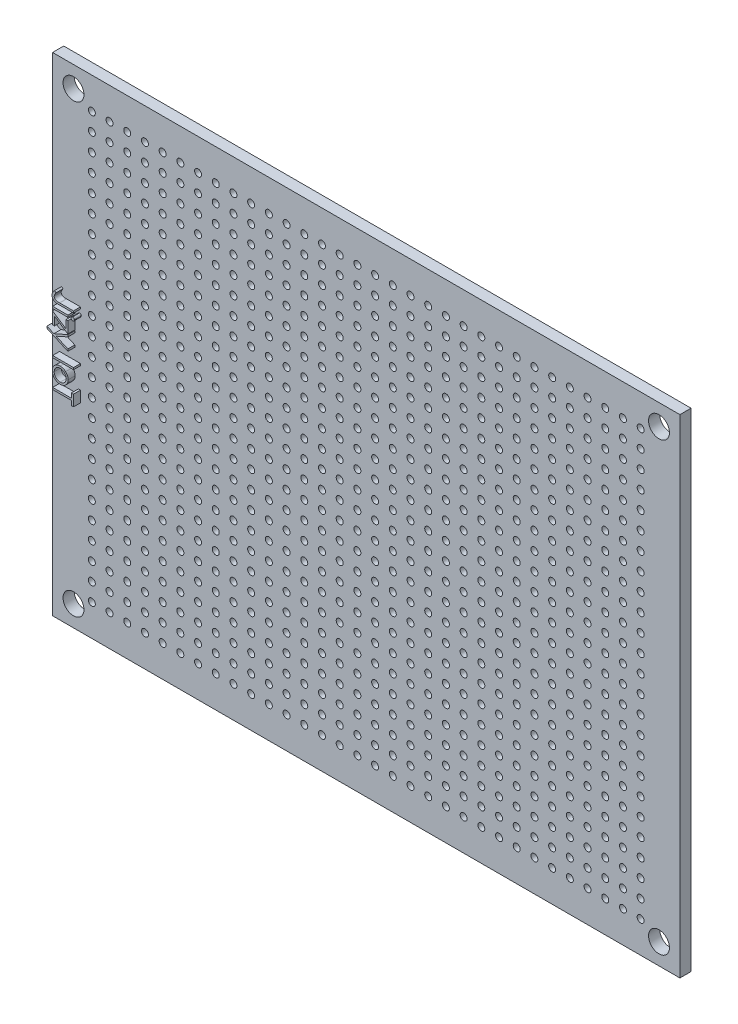
SolidWorks part; units mm, degrees
ref_plane "Front Plane" through (0, 0, 0) normal (0, 0, 1) x (1, 0, 0)
ref_plane "Top Plane" through (0, 0, 0) normal (0, 1, 0) x (1, 0, 0)
ref_plane "Right Plane" through (0, 0, 0) normal (1, 0, 0) x (0, 0, -1)
sketch "Sketch1" plane through (0, 0, 0) normal (0, 0, 1) x (1, 0, 0)
  line L0 (42, 32) -> (-42, 32) construction
  line L1 (45, -35) -> (-45, -35)
  line L2 (45, -35) -> (45, 35)
  line L3 (45, 35) -> (-45, 35)
  line L4 (-45, -35) -> (-45, 35)
  line L5 (45, -35) -> (-45, 35) construction
  line L6 (45, 35) -> (-45, -35) construction
  line L7 (-42, -32) -> (-42, 32) construction
  line L8 (42, -32) -> (-42, -32) construction
  line L9 (42, -32) -> (42, 32) construction
  line L10 (-60.0579, 0) -> (53.9786, 0) construction
  circle A0 centre (-42, 32) radius 1.5
  circle A1 centre (42, 32) radius 1.5
  circle A2 centre (42, -32) radius 1.5
  circle A3 centre (-42, -32) radius 1.5
  circle A4 centre (-39.37, 30.48) radius 0.5
  circle A5 centre (-36.83, 30.48) radius 0.5
  circle A6 centre (-34.29, 30.48) radius 0.5
  circle A7 centre (-31.75, 30.48) radius 0.5
  circle A8 centre (-29.21, 30.48) radius 0.5
  circle A9 centre (-26.67, 30.48) radius 0.5
  circle A10 centre (-24.13, 30.48) radius 0.5
  circle A11 centre (-21.59, 30.48) radius 0.5
  circle A12 centre (-19.05, 30.48) radius 0.5
  circle A13 centre (-16.51, 30.48) radius 0.5
  circle A14 centre (-13.97, 30.48) radius 0.5
  circle A15 centre (-11.43, 30.48) radius 0.5
  circle A16 centre (-8.89, 30.48) radius 0.5
  circle A17 centre (-6.35, 30.48) radius 0.5
  circle A18 centre (-3.81, 30.48) radius 0.5
  circle A19 centre (-1.27, 30.48) radius 0.5
  circle A20 centre (1.27, 30.48) radius 0.5
  circle A21 centre (3.81, 30.48) radius 0.5
  circle A22 centre (6.35, 30.48) radius 0.5
  circle A23 centre (8.89, 30.48) radius 0.5
  circle A24 centre (11.43, 30.48) radius 0.5
  circle A25 centre (13.97, 30.48) radius 0.5
  circle A26 centre (16.51, 30.48) radius 0.5
  circle A27 centre (19.05, 30.48) radius 0.5
  circle A28 centre (21.59, 30.48) radius 0.5
  circle A29 centre (24.13, 30.48) radius 0.5
  circle A30 centre (26.67, 30.48) radius 0.5
  circle A31 centre (29.21, 30.48) radius 0.5
  circle A32 centre (31.75, 30.48) radius 0.5
  circle A33 centre (34.29, 30.48) radius 0.5
  circle A34 centre (36.83, 30.48) radius 0.5
  circle A35 centre (39.37, 30.48) radius 0.5
  circle A36 centre (-36.83, 27.94) radius 0.5
  circle A37 centre (-34.29, 27.94) radius 0.5
  circle A38 centre (-31.75, 27.94) radius 0.5
  circle A39 centre (-29.21, 27.94) radius 0.5
  circle A40 centre (-26.67, 27.94) radius 0.5
  circle A41 centre (-24.13, 27.94) radius 0.5
  circle A42 centre (-21.59, 27.94) radius 0.5
  circle A43 centre (-19.05, 27.94) radius 0.5
  circle A44 centre (-16.51, 27.94) radius 0.5
  circle A45 centre (-13.97, 27.94) radius 0.5
  circle A46 centre (-11.43, 27.94) radius 0.5
  circle A47 centre (-8.89, 27.94) radius 0.5
  circle A48 centre (-6.35, 27.94) radius 0.5
  circle A49 centre (-3.81, 27.94) radius 0.5
  circle A50 centre (-1.27, 27.94) radius 0.5
  circle A51 centre (1.27, 27.94) radius 0.5
  circle A52 centre (3.81, 27.94) radius 0.5
  circle A53 centre (6.35, 27.94) radius 0.5
  circle A54 centre (8.89, 27.94) radius 0.5
  circle A55 centre (11.43, 27.94) radius 0.5
  circle A56 centre (13.97, 27.94) radius 0.5
  circle A57 centre (16.51, 27.94) radius 0.5
  circle A58 centre (19.05, 27.94) radius 0.5
  circle A59 centre (21.59, 27.94) radius 0.5
  circle A60 centre (24.13, 27.94) radius 0.5
  circle A61 centre (26.67, 27.94) radius 0.5
  circle A62 centre (29.21, 27.94) radius 0.5
  circle A63 centre (31.75, 27.94) radius 0.5
  circle A64 centre (34.29, 27.94) radius 0.5
  circle A65 centre (36.83, 27.94) radius 0.5
  circle A66 centre (39.37, 27.94) radius 0.5
  circle A67 centre (-36.83, 25.4) radius 0.5
  circle A68 centre (-34.29, 25.4) radius 0.5
  circle A69 centre (-31.75, 25.4) radius 0.5
  circle A70 centre (-29.21, 25.4) radius 0.5
  circle A71 centre (-26.67, 25.4) radius 0.5
  circle A72 centre (-24.13, 25.4) radius 0.5
  circle A73 centre (-21.59, 25.4) radius 0.5
  circle A74 centre (-19.05, 25.4) radius 0.5
  circle A75 centre (-16.51, 25.4) radius 0.5
  circle A76 centre (-13.97, 25.4) radius 0.5
  circle A77 centre (-11.43, 25.4) radius 0.5
  circle A78 centre (-8.89, 25.4) radius 0.5
  circle A79 centre (-6.35, 25.4) radius 0.5
  circle A80 centre (-3.81, 25.4) radius 0.5
  circle A81 centre (-1.27, 25.4) radius 0.5
  circle A82 centre (1.27, 25.4) radius 0.5
  circle A83 centre (3.81, 25.4) radius 0.5
  circle A84 centre (6.35, 25.4) radius 0.5
  circle A85 centre (8.89, 25.4) radius 0.5
  circle A86 centre (11.43, 25.4) radius 0.5
  circle A87 centre (13.97, 25.4) radius 0.5
  circle A88 centre (16.51, 25.4) radius 0.5
  circle A89 centre (19.05, 25.4) radius 0.5
  circle A90 centre (21.59, 25.4) radius 0.5
  circle A91 centre (24.13, 25.4) radius 0.5
  circle A92 centre (26.67, 25.4) radius 0.5
  circle A93 centre (29.21, 25.4) radius 0.5
  circle A94 centre (31.75, 25.4) radius 0.5
  circle A95 centre (34.29, 25.4) radius 0.5
  circle A96 centre (36.83, 25.4) radius 0.5
  circle A97 centre (39.37, 25.4) radius 0.5
  circle A98 centre (-36.83, 22.86) radius 0.5
  circle A99 centre (-34.29, 22.86) radius 0.5
  circle A100 centre (-31.75, 22.86) radius 0.5
  circle A101 centre (-29.21, 22.86) radius 0.5
  circle A102 centre (-26.67, 22.86) radius 0.5
  circle A103 centre (-24.13, 22.86) radius 0.5
  circle A104 centre (-21.59, 22.86) radius 0.5
  circle A105 centre (-19.05, 22.86) radius 0.5
  circle A106 centre (-16.51, 22.86) radius 0.5
  circle A107 centre (-13.97, 22.86) radius 0.5
  circle A108 centre (-11.43, 22.86) radius 0.5
  circle A109 centre (-8.89, 22.86) radius 0.5
  circle A110 centre (-6.35, 22.86) radius 0.5
  circle A111 centre (-3.81, 22.86) radius 0.5
  circle A112 centre (-1.27, 22.86) radius 0.5
  circle A113 centre (1.27, 22.86) radius 0.5
  circle A114 centre (3.81, 22.86) radius 0.5
  circle A115 centre (6.35, 22.86) radius 0.5
  circle A116 centre (8.89, 22.86) radius 0.5
  circle A117 centre (11.43, 22.86) radius 0.5
  circle A118 centre (13.97, 22.86) radius 0.5
  circle A119 centre (16.51, 22.86) radius 0.5
  circle A120 centre (19.05, 22.86) radius 0.5
  circle A121 centre (21.59, 22.86) radius 0.5
  circle A122 centre (24.13, 22.86) radius 0.5
  circle A123 centre (26.67, 22.86) radius 0.5
  circle A124 centre (29.21, 22.86) radius 0.5
  circle A125 centre (31.75, 22.86) radius 0.5
  circle A126 centre (34.29, 22.86) radius 0.5
  circle A127 centre (36.83, 22.86) radius 0.5
  circle A128 centre (39.37, 22.86) radius 0.5
  circle A129 centre (-36.83, 20.32) radius 0.5
  circle A130 centre (-34.29, 20.32) radius 0.5
  circle A131 centre (-31.75, 20.32) radius 0.5
  circle A132 centre (-29.21, 20.32) radius 0.5
  circle A133 centre (-26.67, 20.32) radius 0.5
  circle A134 centre (-24.13, 20.32) radius 0.5
  circle A135 centre (-21.59, 20.32) radius 0.5
  circle A136 centre (-19.05, 20.32) radius 0.5
  circle A137 centre (-16.51, 20.32) radius 0.5
  circle A138 centre (-13.97, 20.32) radius 0.5
  circle A139 centre (-11.43, 20.32) radius 0.5
  circle A140 centre (-8.89, 20.32) radius 0.5
  circle A141 centre (-6.35, 20.32) radius 0.5
  circle A142 centre (-3.81, 20.32) radius 0.5
  circle A143 centre (-1.27, 20.32) radius 0.5
  circle A144 centre (1.27, 20.32) radius 0.5
  circle A145 centre (3.81, 20.32) radius 0.5
  circle A146 centre (6.35, 20.32) radius 0.5
  circle A147 centre (8.89, 20.32) radius 0.5
  circle A148 centre (11.43, 20.32) radius 0.5
  circle A149 centre (13.97, 20.32) radius 0.5
  circle A150 centre (16.51, 20.32) radius 0.5
  circle A151 centre (19.05, 20.32) radius 0.5
  circle A152 centre (21.59, 20.32) radius 0.5
  circle A153 centre (24.13, 20.32) radius 0.5
  circle A154 centre (26.67, 20.32) radius 0.5
  circle A155 centre (29.21, 20.32) radius 0.5
  circle A156 centre (31.75, 20.32) radius 0.5
  circle A157 centre (34.29, 20.32) radius 0.5
  circle A158 centre (36.83, 20.32) radius 0.5
  circle A159 centre (39.37, 20.32) radius 0.5
  circle A160 centre (-36.83, 17.78) radius 0.5
  circle A161 centre (-34.29, 17.78) radius 0.5
  circle A162 centre (-31.75, 17.78) radius 0.5
  circle A163 centre (-29.21, 17.78) radius 0.5
  circle A164 centre (-26.67, 17.78) radius 0.5
  circle A165 centre (-24.13, 17.78) radius 0.5
  circle A166 centre (-21.59, 17.78) radius 0.5
  circle A167 centre (-19.05, 17.78) radius 0.5
  circle A168 centre (-16.51, 17.78) radius 0.5
  circle A169 centre (-13.97, 17.78) radius 0.5
  circle A170 centre (-11.43, 17.78) radius 0.5
  circle A171 centre (-8.89, 17.78) radius 0.5
  circle A172 centre (-6.35, 17.78) radius 0.5
  circle A173 centre (-3.81, 17.78) radius 0.5
  circle A174 centre (-1.27, 17.78) radius 0.5
  circle A175 centre (1.27, 17.78) radius 0.5
  circle A176 centre (3.81, 17.78) radius 0.5
  circle A177 centre (6.35, 17.78) radius 0.5
  circle A178 centre (8.89, 17.78) radius 0.5
  circle A179 centre (11.43, 17.78) radius 0.5
  circle A180 centre (13.97, 17.78) radius 0.5
  circle A181 centre (16.51, 17.78) radius 0.5
  circle A182 centre (19.05, 17.78) radius 0.5
  circle A183 centre (21.59, 17.78) radius 0.5
  circle A184 centre (24.13, 17.78) radius 0.5
  circle A185 centre (26.67, 17.78) radius 0.5
  circle A186 centre (29.21, 17.78) radius 0.5
  circle A187 centre (31.75, 17.78) radius 0.5
  circle A188 centre (34.29, 17.78) radius 0.5
  circle A189 centre (36.83, 17.78) radius 0.5
  circle A190 centre (39.37, 17.78) radius 0.5
  circle A191 centre (-36.83, 15.24) radius 0.5
  circle A192 centre (-34.29, 15.24) radius 0.5
  circle A193 centre (-31.75, 15.24) radius 0.5
  circle A194 centre (-29.21, 15.24) radius 0.5
  circle A195 centre (-26.67, 15.24) radius 0.5
  circle A196 centre (-24.13, 15.24) radius 0.5
  circle A197 centre (-21.59, 15.24) radius 0.5
  circle A198 centre (-19.05, 15.24) radius 0.5
  circle A199 centre (-16.51, 15.24) radius 0.5
  circle A200 centre (-13.97, 15.24) radius 0.5
  circle A201 centre (-11.43, 15.24) radius 0.5
  circle A202 centre (-8.89, 15.24) radius 0.5
  circle A203 centre (-6.35, 15.24) radius 0.5
  circle A204 centre (-3.81, 15.24) radius 0.5
  circle A205 centre (-1.27, 15.24) radius 0.5
  circle A206 centre (1.27, 15.24) radius 0.5
  circle A207 centre (3.81, 15.24) radius 0.5
  circle A208 centre (6.35, 15.24) radius 0.5
  circle A209 centre (8.89, 15.24) radius 0.5
  circle A210 centre (11.43, 15.24) radius 0.5
  circle A211 centre (13.97, 15.24) radius 0.5
  circle A212 centre (16.51, 15.24) radius 0.5
  circle A213 centre (19.05, 15.24) radius 0.5
  circle A214 centre (21.59, 15.24) radius 0.5
  circle A215 centre (24.13, 15.24) radius 0.5
  circle A216 centre (26.67, 15.24) radius 0.5
  circle A217 centre (29.21, 15.24) radius 0.5
  circle A218 centre (31.75, 15.24) radius 0.5
  circle A219 centre (34.29, 15.24) radius 0.5
  circle A220 centre (36.83, 15.24) radius 0.5
  circle A221 centre (39.37, 15.24) radius 0.5
  circle A222 centre (-36.83, 12.7) radius 0.5
  circle A223 centre (-34.29, 12.7) radius 0.5
  circle A224 centre (-31.75, 12.7) radius 0.5
  circle A225 centre (-29.21, 12.7) radius 0.5
  circle A226 centre (-26.67, 12.7) radius 0.5
  circle A227 centre (-24.13, 12.7) radius 0.5
  circle A228 centre (-21.59, 12.7) radius 0.5
  circle A229 centre (-19.05, 12.7) radius 0.5
  circle A230 centre (-16.51, 12.7) radius 0.5
  circle A231 centre (-13.97, 12.7) radius 0.5
  circle A232 centre (-11.43, 12.7) radius 0.5
  circle A233 centre (-8.89, 12.7) radius 0.5
  circle A234 centre (-6.35, 12.7) radius 0.5
  circle A235 centre (-3.81, 12.7) radius 0.5
  circle A236 centre (-1.27, 12.7) radius 0.5
  circle A237 centre (1.27, 12.7) radius 0.5
  circle A238 centre (3.81, 12.7) radius 0.5
  circle A239 centre (6.35, 12.7) radius 0.5
  circle A240 centre (8.89, 12.7) radius 0.5
  circle A241 centre (11.43, 12.7) radius 0.5
  circle A242 centre (13.97, 12.7) radius 0.5
  circle A243 centre (16.51, 12.7) radius 0.5
  circle A244 centre (19.05, 12.7) radius 0.5
  circle A245 centre (21.59, 12.7) radius 0.5
  circle A246 centre (24.13, 12.7) radius 0.5
  circle A247 centre (26.67, 12.7) radius 0.5
  circle A248 centre (29.21, 12.7) radius 0.5
  circle A249 centre (31.75, 12.7) radius 0.5
  circle A250 centre (34.29, 12.7) radius 0.5
  circle A251 centre (36.83, 12.7) radius 0.5
  circle A252 centre (39.37, 12.7) radius 0.5
  circle A253 centre (-36.83, 10.16) radius 0.5
  circle A254 centre (-34.29, 10.16) radius 0.5
  circle A255 centre (-31.75, 10.16) radius 0.5
  circle A256 centre (-29.21, 10.16) radius 0.5
  circle A257 centre (-26.67, 10.16) radius 0.5
  circle A258 centre (-24.13, 10.16) radius 0.5
  circle A259 centre (-21.59, 10.16) radius 0.5
  circle A260 centre (-19.05, 10.16) radius 0.5
  circle A261 centre (-16.51, 10.16) radius 0.5
  circle A262 centre (-13.97, 10.16) radius 0.5
  circle A263 centre (-11.43, 10.16) radius 0.5
  circle A264 centre (-8.89, 10.16) radius 0.5
  circle A265 centre (-6.35, 10.16) radius 0.5
  circle A266 centre (-3.81, 10.16) radius 0.5
  circle A267 centre (-1.27, 10.16) radius 0.5
  circle A268 centre (1.27, 10.16) radius 0.5
  circle A269 centre (3.81, 10.16) radius 0.5
  circle A270 centre (6.35, 10.16) radius 0.5
  circle A271 centre (8.89, 10.16) radius 0.5
  circle A272 centre (11.43, 10.16) radius 0.5
  circle A273 centre (13.97, 10.16) radius 0.5
  circle A274 centre (16.51, 10.16) radius 0.5
  circle A275 centre (19.05, 10.16) radius 0.5
  circle A276 centre (21.59, 10.16) radius 0.5
  circle A277 centre (24.13, 10.16) radius 0.5
  circle A278 centre (26.67, 10.16) radius 0.5
  circle A279 centre (29.21, 10.16) radius 0.5
  circle A280 centre (31.75, 10.16) radius 0.5
  circle A281 centre (34.29, 10.16) radius 0.5
  circle A282 centre (36.83, 10.16) radius 0.5
  circle A283 centre (39.37, 10.16) radius 0.5
  circle A284 centre (-36.83, 7.62) radius 0.5
  circle A285 centre (-34.29, 7.62) radius 0.5
  circle A286 centre (-31.75, 7.62) radius 0.5
  circle A287 centre (-29.21, 7.62) radius 0.5
  circle A288 centre (-26.67, 7.62) radius 0.5
  circle A289 centre (-24.13, 7.62) radius 0.5
  circle A290 centre (-21.59, 7.62) radius 0.5
  circle A291 centre (-19.05, 7.62) radius 0.5
  circle A292 centre (-16.51, 7.62) radius 0.5
  circle A293 centre (-13.97, 7.62) radius 0.5
  circle A294 centre (-11.43, 7.62) radius 0.5
  circle A295 centre (-8.89, 7.62) radius 0.5
  circle A296 centre (-6.35, 7.62) radius 0.5
  circle A297 centre (-3.81, 7.62) radius 0.5
  circle A298 centre (-1.27, 7.62) radius 0.5
  circle A299 centre (1.27, 7.62) radius 0.5
  circle A300 centre (3.81, 7.62) radius 0.5
  circle A301 centre (6.35, 7.62) radius 0.5
  circle A302 centre (8.89, 7.62) radius 0.5
  circle A303 centre (11.43, 7.62) radius 0.5
  circle A304 centre (13.97, 7.62) radius 0.5
  circle A305 centre (16.51, 7.62) radius 0.5
  circle A306 centre (19.05, 7.62) radius 0.5
  circle A307 centre (21.59, 7.62) radius 0.5
  circle A308 centre (24.13, 7.62) radius 0.5
  circle A309 centre (26.67, 7.62) radius 0.5
  circle A310 centre (29.21, 7.62) radius 0.5
  circle A311 centre (31.75, 7.62) radius 0.5
  circle A312 centre (34.29, 7.62) radius 0.5
  circle A313 centre (36.83, 7.62) radius 0.5
  circle A314 centre (39.37, 7.62) radius 0.5
  circle A315 centre (-36.83, 5.08) radius 0.5
  circle A316 centre (-34.29, 5.08) radius 0.5
  circle A317 centre (-31.75, 5.08) radius 0.5
  circle A318 centre (-29.21, 5.08) radius 0.5
  circle A319 centre (-26.67, 5.08) radius 0.5
  circle A320 centre (-24.13, 5.08) radius 0.5
  circle A321 centre (-21.59, 5.08) radius 0.5
  circle A322 centre (-19.05, 5.08) radius 0.5
  circle A323 centre (-16.51, 5.08) radius 0.5
  circle A324 centre (-13.97, 5.08) radius 0.5
  circle A325 centre (-11.43, 5.08) radius 0.5
  circle A326 centre (-8.89, 5.08) radius 0.5
  circle A327 centre (-6.35, 5.08) radius 0.5
  circle A328 centre (-3.81, 5.08) radius 0.5
  circle A329 centre (-1.27, 5.08) radius 0.5
  circle A330 centre (1.27, 5.08) radius 0.5
  circle A331 centre (3.81, 5.08) radius 0.5
  circle A332 centre (6.35, 5.08) radius 0.5
  circle A333 centre (8.89, 5.08) radius 0.5
  circle A334 centre (11.43, 5.08) radius 0.5
  circle A335 centre (13.97, 5.08) radius 0.5
  circle A336 centre (16.51, 5.08) radius 0.5
  circle A337 centre (19.05, 5.08) radius 0.5
  circle A338 centre (21.59, 5.08) radius 0.5
  circle A339 centre (24.13, 5.08) radius 0.5
  circle A340 centre (26.67, 5.08) radius 0.5
  circle A341 centre (29.21, 5.08) radius 0.5
  circle A342 centre (31.75, 5.08) radius 0.5
  circle A343 centre (34.29, 5.08) radius 0.5
  circle A344 centre (36.83, 5.08) radius 0.5
  circle A345 centre (39.37, 5.08) radius 0.5
  circle A346 centre (-36.83, 2.54) radius 0.5
  circle A347 centre (-34.29, 2.54) radius 0.5
  circle A348 centre (-31.75, 2.54) radius 0.5
  circle A349 centre (-29.21, 2.54) radius 0.5
  circle A350 centre (-26.67, 2.54) radius 0.5
  circle A351 centre (-24.13, 2.54) radius 0.5
  circle A352 centre (-21.59, 2.54) radius 0.5
  circle A353 centre (-19.05, 2.54) radius 0.5
  circle A354 centre (-16.51, 2.54) radius 0.5
  circle A355 centre (-13.97, 2.54) radius 0.5
  circle A356 centre (-11.43, 2.54) radius 0.5
  circle A357 centre (-8.89, 2.54) radius 0.5
  circle A358 centre (-6.35, 2.54) radius 0.5
  circle A359 centre (-3.81, 2.54) radius 0.5
  circle A360 centre (-1.27, 2.54) radius 0.5
  circle A361 centre (1.27, 2.54) radius 0.5
  circle A362 centre (3.81, 2.54) radius 0.5
  circle A363 centre (6.35, 2.54) radius 0.5
  circle A364 centre (8.89, 2.54) radius 0.5
  circle A365 centre (11.43, 2.54) radius 0.5
  circle A366 centre (13.97, 2.54) radius 0.5
  circle A367 centre (16.51, 2.54) radius 0.5
  circle A368 centre (19.05, 2.54) radius 0.5
  circle A369 centre (21.59, 2.54) radius 0.5
  circle A370 centre (24.13, 2.54) radius 0.5
  circle A371 centre (26.67, 2.54) radius 0.5
  circle A372 centre (29.21, 2.54) radius 0.5
  circle A373 centre (31.75, 2.54) radius 0.5
  circle A374 centre (34.29, 2.54) radius 0.5
  circle A375 centre (36.83, 2.54) radius 0.5
  circle A376 centre (39.37, 2.54) radius 0.5
  circle A377 centre (-36.83, 0) radius 0.5
  circle A378 centre (-34.29, 0) radius 0.5
  circle A379 centre (-31.75, 0) radius 0.5
  circle A380 centre (-29.21, 0) radius 0.5
  circle A381 centre (-26.67, 0) radius 0.5
  circle A382 centre (-24.13, 0) radius 0.5
  circle A383 centre (-21.59, 0) radius 0.5
  circle A384 centre (-19.05, 0) radius 0.5
  circle A385 centre (-16.51, 0) radius 0.5
  circle A386 centre (-13.97, 0) radius 0.5
  circle A387 centre (-11.43, 0) radius 0.5
  circle A388 centre (-8.89, 0) radius 0.5
  circle A389 centre (-6.35, 0) radius 0.5
  circle A390 centre (-3.81, 0) radius 0.5
  circle A391 centre (-1.27, 0) radius 0.5
  circle A392 centre (1.27, 0) radius 0.5
  circle A393 centre (3.81, 0) radius 0.5
  circle A394 centre (6.35, 0) radius 0.5
  circle A395 centre (8.89, 0) radius 0.5
  circle A396 centre (11.43, 0) radius 0.5
  circle A397 centre (13.97, 0) radius 0.5
  circle A398 centre (16.51, 0) radius 0.5
  circle A399 centre (19.05, 0) radius 0.5
  circle A400 centre (21.59, 0) radius 0.5
  circle A401 centre (24.13, 0) radius 0.5
  circle A402 centre (26.67, 0) radius 0.5
  circle A403 centre (29.21, 0) radius 0.5
  circle A404 centre (31.75, 0) radius 0.5
  circle A405 centre (34.29, 0) radius 0.5
  circle A406 centre (36.83, 0) radius 0.5
  circle A407 centre (39.37, 0) radius 0.5
  circle A408 centre (-36.83, -2.54) radius 0.5
  circle A409 centre (-34.29, -2.54) radius 0.5
  circle A410 centre (-31.75, -2.54) radius 0.5
  circle A411 centre (-29.21, -2.54) radius 0.5
  circle A412 centre (-26.67, -2.54) radius 0.5
  circle A413 centre (-24.13, -2.54) radius 0.5
  circle A414 centre (-21.59, -2.54) radius 0.5
  circle A415 centre (-19.05, -2.54) radius 0.5
  circle A416 centre (-16.51, -2.54) radius 0.5
  circle A417 centre (-13.97, -2.54) radius 0.5
  circle A418 centre (-11.43, -2.54) radius 0.5
  circle A419 centre (-8.89, -2.54) radius 0.5
  circle A420 centre (-6.35, -2.54) radius 0.5
  circle A421 centre (-3.81, -2.54) radius 0.5
  circle A422 centre (-1.27, -2.54) radius 0.5
  circle A423 centre (1.27, -2.54) radius 0.5
  circle A424 centre (3.81, -2.54) radius 0.5
  circle A425 centre (6.35, -2.54) radius 0.5
  circle A426 centre (8.89, -2.54) radius 0.5
  circle A427 centre (11.43, -2.54) radius 0.5
  circle A428 centre (13.97, -2.54) radius 0.5
  circle A429 centre (16.51, -2.54) radius 0.5
  circle A430 centre (19.05, -2.54) radius 0.5
  circle A431 centre (21.59, -2.54) radius 0.5
  circle A432 centre (24.13, -2.54) radius 0.5
  circle A433 centre (26.67, -2.54) radius 0.5
  circle A434 centre (29.21, -2.54) radius 0.5
  circle A435 centre (31.75, -2.54) radius 0.5
  circle A436 centre (34.29, -2.54) radius 0.5
  circle A437 centre (36.83, -2.54) radius 0.5
  circle A438 centre (39.37, -2.54) radius 0.5
  circle A439 centre (-36.83, -5.08) radius 0.5
  circle A440 centre (-34.29, -5.08) radius 0.5
  circle A441 centre (-31.75, -5.08) radius 0.5
  circle A442 centre (-29.21, -5.08) radius 0.5
  circle A443 centre (-26.67, -5.08) radius 0.5
  circle A444 centre (-24.13, -5.08) radius 0.5
  circle A445 centre (-21.59, -5.08) radius 0.5
  circle A446 centre (-19.05, -5.08) radius 0.5
  circle A447 centre (-16.51, -5.08) radius 0.5
  circle A448 centre (-13.97, -5.08) radius 0.5
  circle A449 centre (-11.43, -5.08) radius 0.5
  circle A450 centre (-8.89, -5.08) radius 0.5
  circle A451 centre (-6.35, -5.08) radius 0.5
  circle A452 centre (-3.81, -5.08) radius 0.5
  circle A453 centre (-1.27, -5.08) radius 0.5
  circle A454 centre (1.27, -5.08) radius 0.5
  circle A455 centre (3.81, -5.08) radius 0.5
  circle A456 centre (6.35, -5.08) radius 0.5
  circle A457 centre (8.89, -5.08) radius 0.5
  circle A458 centre (11.43, -5.08) radius 0.5
  circle A459 centre (13.97, -5.08) radius 0.5
  circle A460 centre (16.51, -5.08) radius 0.5
  circle A461 centre (19.05, -5.08) radius 0.5
  circle A462 centre (21.59, -5.08) radius 0.5
  circle A463 centre (24.13, -5.08) radius 0.5
  circle A464 centre (26.67, -5.08) radius 0.5
  circle A465 centre (29.21, -5.08) radius 0.5
  circle A466 centre (31.75, -5.08) radius 0.5
  circle A467 centre (34.29, -5.08) radius 0.5
  circle A468 centre (36.83, -5.08) radius 0.5
  circle A469 centre (39.37, -5.08) radius 0.5
  circle A470 centre (-36.83, -7.62) radius 0.5
  circle A471 centre (-34.29, -7.62) radius 0.5
  circle A472 centre (-31.75, -7.62) radius 0.5
  circle A473 centre (-29.21, -7.62) radius 0.5
  circle A474 centre (-26.67, -7.62) radius 0.5
  circle A475 centre (-24.13, -7.62) radius 0.5
  circle A476 centre (-21.59, -7.62) radius 0.5
  circle A477 centre (-19.05, -7.62) radius 0.5
  circle A478 centre (-16.51, -7.62) radius 0.5
  circle A479 centre (-13.97, -7.62) radius 0.5
  circle A480 centre (-11.43, -7.62) radius 0.5
  circle A481 centre (-8.89, -7.62) radius 0.5
  circle A482 centre (-6.35, -7.62) radius 0.5
  circle A483 centre (-3.81, -7.62) radius 0.5
  circle A484 centre (-1.27, -7.62) radius 0.5
  circle A485 centre (1.27, -7.62) radius 0.5
  circle A486 centre (3.81, -7.62) radius 0.5
  circle A487 centre (6.35, -7.62) radius 0.5
  circle A488 centre (8.89, -7.62) radius 0.5
  circle A489 centre (11.43, -7.62) radius 0.5
  circle A490 centre (13.97, -7.62) radius 0.5
  circle A491 centre (16.51, -7.62) radius 0.5
  circle A492 centre (19.05, -7.62) radius 0.5
  circle A493 centre (21.59, -7.62) radius 0.5
  circle A494 centre (24.13, -7.62) radius 0.5
  circle A495 centre (26.67, -7.62) radius 0.5
  circle A496 centre (29.21, -7.62) radius 0.5
  circle A497 centre (31.75, -7.62) radius 0.5
  circle A498 centre (34.29, -7.62) radius 0.5
  circle A499 centre (36.83, -7.62) radius 0.5
  circle A500 centre (39.37, -7.62) radius 0.5
  circle A501 centre (-36.83, -10.16) radius 0.5
  circle A502 centre (-34.29, -10.16) radius 0.5
  circle A503 centre (-31.75, -10.16) radius 0.5
  circle A504 centre (-29.21, -10.16) radius 0.5
  circle A505 centre (-26.67, -10.16) radius 0.5
  circle A506 centre (-24.13, -10.16) radius 0.5
  circle A507 centre (-21.59, -10.16) radius 0.5
  circle A508 centre (-19.05, -10.16) radius 0.5
  circle A509 centre (-16.51, -10.16) radius 0.5
  circle A510 centre (-13.97, -10.16) radius 0.5
  circle A511 centre (-11.43, -10.16) radius 0.5
  circle A512 centre (-8.89, -10.16) radius 0.5
  circle A513 centre (-6.35, -10.16) radius 0.5
  circle A514 centre (-3.81, -10.16) radius 0.5
  circle A515 centre (-1.27, -10.16) radius 0.5
  circle A516 centre (1.27, -10.16) radius 0.5
  circle A517 centre (3.81, -10.16) radius 0.5
  circle A518 centre (6.35, -10.16) radius 0.5
  circle A519 centre (8.89, -10.16) radius 0.5
  circle A520 centre (11.43, -10.16) radius 0.5
  circle A521 centre (13.97, -10.16) radius 0.5
  circle A522 centre (16.51, -10.16) radius 0.5
  circle A523 centre (19.05, -10.16) radius 0.5
  circle A524 centre (21.59, -10.16) radius 0.5
  circle A525 centre (24.13, -10.16) radius 0.5
  circle A526 centre (26.67, -10.16) radius 0.5
  circle A527 centre (29.21, -10.16) radius 0.5
  circle A528 centre (31.75, -10.16) radius 0.5
  circle A529 centre (34.29, -10.16) radius 0.5
  circle A530 centre (36.83, -10.16) radius 0.5
  circle A531 centre (39.37, -10.16) radius 0.5
  circle A532 centre (-36.83, -12.7) radius 0.5
  circle A533 centre (-34.29, -12.7) radius 0.5
  circle A534 centre (-31.75, -12.7) radius 0.5
  circle A535 centre (-29.21, -12.7) radius 0.5
  circle A536 centre (-26.67, -12.7) radius 0.5
  circle A537 centre (-24.13, -12.7) radius 0.5
  circle A538 centre (-21.59, -12.7) radius 0.5
  circle A539 centre (-19.05, -12.7) radius 0.5
  circle A540 centre (-16.51, -12.7) radius 0.5
  circle A541 centre (-13.97, -12.7) radius 0.5
  circle A542 centre (-11.43, -12.7) radius 0.5
  circle A543 centre (-8.89, -12.7) radius 0.5
  circle A544 centre (-6.35, -12.7) radius 0.5
  circle A545 centre (-3.81, -12.7) radius 0.5
  circle A546 centre (-1.27, -12.7) radius 0.5
  circle A547 centre (1.27, -12.7) radius 0.5
  circle A548 centre (3.81, -12.7) radius 0.5
  circle A549 centre (6.35, -12.7) radius 0.5
  circle A550 centre (8.89, -12.7) radius 0.5
  circle A551 centre (11.43, -12.7) radius 0.5
  circle A552 centre (13.97, -12.7) radius 0.5
  circle A553 centre (16.51, -12.7) radius 0.5
  circle A554 centre (19.05, -12.7) radius 0.5
  circle A555 centre (21.59, -12.7) radius 0.5
  circle A556 centre (24.13, -12.7) radius 0.5
  circle A557 centre (26.67, -12.7) radius 0.5
  circle A558 centre (29.21, -12.7) radius 0.5
  circle A559 centre (31.75, -12.7) radius 0.5
  circle A560 centre (34.29, -12.7) radius 0.5
  circle A561 centre (36.83, -12.7) radius 0.5
  circle A562 centre (39.37, -12.7) radius 0.5
  circle A563 centre (-36.83, -15.24) radius 0.5
  circle A564 centre (-34.29, -15.24) radius 0.5
  circle A565 centre (-31.75, -15.24) radius 0.5
  circle A566 centre (-29.21, -15.24) radius 0.5
  circle A567 centre (-26.67, -15.24) radius 0.5
  circle A568 centre (-24.13, -15.24) radius 0.5
  circle A569 centre (-21.59, -15.24) radius 0.5
  circle A570 centre (-19.05, -15.24) radius 0.5
  circle A571 centre (-16.51, -15.24) radius 0.5
  circle A572 centre (-13.97, -15.24) radius 0.5
  circle A573 centre (-11.43, -15.24) radius 0.5
  circle A574 centre (-8.89, -15.24) radius 0.5
  circle A575 centre (-6.35, -15.24) radius 0.5
  circle A576 centre (-3.81, -15.24) radius 0.5
  circle A577 centre (-1.27, -15.24) radius 0.5
  circle A578 centre (1.27, -15.24) radius 0.5
  circle A579 centre (3.81, -15.24) radius 0.5
  circle A580 centre (6.35, -15.24) radius 0.5
  circle A581 centre (8.89, -15.24) radius 0.5
  circle A582 centre (11.43, -15.24) radius 0.5
  circle A583 centre (13.97, -15.24) radius 0.5
  circle A584 centre (16.51, -15.24) radius 0.5
  circle A585 centre (19.05, -15.24) radius 0.5
  circle A586 centre (21.59, -15.24) radius 0.5
  circle A587 centre (24.13, -15.24) radius 0.5
  circle A588 centre (26.67, -15.24) radius 0.5
  circle A589 centre (29.21, -15.24) radius 0.5
  circle A590 centre (31.75, -15.24) radius 0.5
  circle A591 centre (34.29, -15.24) radius 0.5
  circle A592 centre (36.83, -15.24) radius 0.5
  circle A593 centre (39.37, -15.24) radius 0.5
  circle A594 centre (-36.83, -17.78) radius 0.5
  circle A595 centre (-34.29, -17.78) radius 0.5
  circle A596 centre (-31.75, -17.78) radius 0.5
  circle A597 centre (-29.21, -17.78) radius 0.5
  circle A598 centre (-26.67, -17.78) radius 0.5
  circle A599 centre (-24.13, -17.78) radius 0.5
  circle A600 centre (-21.59, -17.78) radius 0.5
  circle A601 centre (-19.05, -17.78) radius 0.5
  circle A602 centre (-16.51, -17.78) radius 0.5
  circle A603 centre (-13.97, -17.78) radius 0.5
  circle A604 centre (-11.43, -17.78) radius 0.5
  circle A605 centre (-8.89, -17.78) radius 0.5
  circle A606 centre (-6.35, -17.78) radius 0.5
  circle A607 centre (-3.81, -17.78) radius 0.5
  circle A608 centre (-1.27, -17.78) radius 0.5
  circle A609 centre (1.27, -17.78) radius 0.5
  circle A610 centre (3.81, -17.78) radius 0.5
  circle A611 centre (6.35, -17.78) radius 0.5
  circle A612 centre (8.89, -17.78) radius 0.5
  circle A613 centre (11.43, -17.78) radius 0.5
  circle A614 centre (13.97, -17.78) radius 0.5
  circle A615 centre (16.51, -17.78) radius 0.5
  circle A616 centre (19.05, -17.78) radius 0.5
  circle A617 centre (21.59, -17.78) radius 0.5
  circle A618 centre (24.13, -17.78) radius 0.5
  circle A619 centre (26.67, -17.78) radius 0.5
  circle A620 centre (29.21, -17.78) radius 0.5
  circle A621 centre (31.75, -17.78) radius 0.5
  circle A622 centre (34.29, -17.78) radius 0.5
  circle A623 centre (36.83, -17.78) radius 0.5
  circle A624 centre (39.37, -17.78) radius 0.5
  circle A625 centre (-36.83, -20.32) radius 0.5
  circle A626 centre (-34.29, -20.32) radius 0.5
  circle A627 centre (-31.75, -20.32) radius 0.5
  circle A628 centre (-29.21, -20.32) radius 0.5
  circle A629 centre (-26.67, -20.32) radius 0.5
  circle A630 centre (-24.13, -20.32) radius 0.5
  circle A631 centre (-21.59, -20.32) radius 0.5
  circle A632 centre (-19.05, -20.32) radius 0.5
  circle A633 centre (-16.51, -20.32) radius 0.5
  circle A634 centre (-13.97, -20.32) radius 0.5
  circle A635 centre (-11.43, -20.32) radius 0.5
  circle A636 centre (-8.89, -20.32) radius 0.5
  circle A637 centre (-6.35, -20.32) radius 0.5
  circle A638 centre (-3.81, -20.32) radius 0.5
  circle A639 centre (-1.27, -20.32) radius 0.5
  circle A640 centre (1.27, -20.32) radius 0.5
  circle A641 centre (3.81, -20.32) radius 0.5
  circle A642 centre (6.35, -20.32) radius 0.5
  circle A643 centre (8.89, -20.32) radius 0.5
  circle A644 centre (11.43, -20.32) radius 0.5
  circle A645 centre (13.97, -20.32) radius 0.5
  circle A646 centre (16.51, -20.32) radius 0.5
  circle A647 centre (19.05, -20.32) radius 0.5
  circle A648 centre (21.59, -20.32) radius 0.5
  circle A649 centre (24.13, -20.32) radius 0.5
  circle A650 centre (26.67, -20.32) radius 0.5
  circle A651 centre (29.21, -20.32) radius 0.5
  circle A652 centre (31.75, -20.32) radius 0.5
  circle A653 centre (34.29, -20.32) radius 0.5
  circle A654 centre (36.83, -20.32) radius 0.5
  circle A655 centre (39.37, -20.32) radius 0.5
  circle A656 centre (-36.83, -22.86) radius 0.5
  circle A657 centre (-34.29, -22.86) radius 0.5
  circle A658 centre (-31.75, -22.86) radius 0.5
  circle A659 centre (-29.21, -22.86) radius 0.5
  circle A660 centre (-26.67, -22.86) radius 0.5
  circle A661 centre (-24.13, -22.86) radius 0.5
  circle A662 centre (-21.59, -22.86) radius 0.5
  circle A663 centre (-19.05, -22.86) radius 0.5
  circle A664 centre (-16.51, -22.86) radius 0.5
  circle A665 centre (-13.97, -22.86) radius 0.5
  circle A666 centre (-11.43, -22.86) radius 0.5
  circle A667 centre (-8.89, -22.86) radius 0.5
  circle A668 centre (-6.35, -22.86) radius 0.5
  circle A669 centre (-3.81, -22.86) radius 0.5
  circle A670 centre (-1.27, -22.86) radius 0.5
  circle A671 centre (1.27, -22.86) radius 0.5
  circle A672 centre (3.81, -22.86) radius 0.5
  circle A673 centre (6.35, -22.86) radius 0.5
  circle A674 centre (8.89, -22.86) radius 0.5
  circle A675 centre (11.43, -22.86) radius 0.5
  circle A676 centre (13.97, -22.86) radius 0.5
  circle A677 centre (16.51, -22.86) radius 0.5
  circle A678 centre (19.05, -22.86) radius 0.5
  circle A679 centre (21.59, -22.86) radius 0.5
  circle A680 centre (24.13, -22.86) radius 0.5
  circle A681 centre (26.67, -22.86) radius 0.5
  circle A682 centre (29.21, -22.86) radius 0.5
  circle A683 centre (31.75, -22.86) radius 0.5
  circle A684 centre (34.29, -22.86) radius 0.5
  circle A685 centre (36.83, -22.86) radius 0.5
  circle A686 centre (39.37, -22.86) radius 0.5
  circle A687 centre (-36.83, -25.4) radius 0.5
  circle A688 centre (-34.29, -25.4) radius 0.5
  circle A689 centre (-31.75, -25.4) radius 0.5
  circle A690 centre (-29.21, -25.4) radius 0.5
  circle A691 centre (-26.67, -25.4) radius 0.5
  circle A692 centre (-24.13, -25.4) radius 0.5
  circle A693 centre (-21.59, -25.4) radius 0.5
  circle A694 centre (-19.05, -25.4) radius 0.5
  circle A695 centre (-16.51, -25.4) radius 0.5
  circle A696 centre (-13.97, -25.4) radius 0.5
  circle A697 centre (-11.43, -25.4) radius 0.5
  circle A698 centre (-8.89, -25.4) radius 0.5
  circle A699 centre (-6.35, -25.4) radius 0.5
  circle A700 centre (-3.81, -25.4) radius 0.5
  circle A701 centre (-1.27, -25.4) radius 0.5
  circle A702 centre (1.27, -25.4) radius 0.5
  circle A703 centre (3.81, -25.4) radius 0.5
  circle A704 centre (6.35, -25.4) radius 0.5
  circle A705 centre (8.89, -25.4) radius 0.5
  circle A706 centre (11.43, -25.4) radius 0.5
  circle A707 centre (13.97, -25.4) radius 0.5
  circle A708 centre (16.51, -25.4) radius 0.5
  circle A709 centre (19.05, -25.4) radius 0.5
  circle A710 centre (21.59, -25.4) radius 0.5
  circle A711 centre (24.13, -25.4) radius 0.5
  circle A712 centre (26.67, -25.4) radius 0.5
  circle A713 centre (29.21, -25.4) radius 0.5
  circle A714 centre (31.75, -25.4) radius 0.5
  circle A715 centre (34.29, -25.4) radius 0.5
  circle A716 centre (36.83, -25.4) radius 0.5
  circle A717 centre (39.37, -25.4) radius 0.5
  circle A718 centre (-36.83, -27.94) radius 0.5
  circle A719 centre (-34.29, -27.94) radius 0.5
  circle A720 centre (-31.75, -27.94) radius 0.5
  circle A721 centre (-29.21, -27.94) radius 0.5
  circle A722 centre (-26.67, -27.94) radius 0.5
  circle A723 centre (-24.13, -27.94) radius 0.5
  circle A724 centre (-21.59, -27.94) radius 0.5
  circle A725 centre (-19.05, -27.94) radius 0.5
  circle A726 centre (-16.51, -27.94) radius 0.5
  circle A727 centre (-13.97, -27.94) radius 0.5
  circle A728 centre (-11.43, -27.94) radius 0.5
  circle A729 centre (-8.89, -27.94) radius 0.5
  circle A730 centre (-6.35, -27.94) radius 0.5
  circle A731 centre (-3.81, -27.94) radius 0.5
  circle A732 centre (-1.27, -27.94) radius 0.5
  circle A733 centre (1.27, -27.94) radius 0.5
  circle A734 centre (3.81, -27.94) radius 0.5
  circle A735 centre (6.35, -27.94) radius 0.5
  circle A736 centre (8.89, -27.94) radius 0.5
  circle A737 centre (11.43, -27.94) radius 0.5
  circle A738 centre (13.97, -27.94) radius 0.5
  circle A739 centre (16.51, -27.94) radius 0.5
  circle A740 centre (19.05, -27.94) radius 0.5
  circle A741 centre (21.59, -27.94) radius 0.5
  circle A742 centre (24.13, -27.94) radius 0.5
  circle A743 centre (26.67, -27.94) radius 0.5
  circle A744 centre (29.21, -27.94) radius 0.5
  circle A745 centre (31.75, -27.94) radius 0.5
  circle A746 centre (34.29, -27.94) radius 0.5
  circle A747 centre (36.83, -27.94) radius 0.5
  circle A748 centre (39.37, -27.94) radius 0.5
  circle A749 centre (-36.83, -30.48) radius 0.5
  circle A750 centre (-34.29, -30.48) radius 0.5
  circle A751 centre (-31.75, -30.48) radius 0.5
  circle A752 centre (-29.21, -30.48) radius 0.5
  circle A753 centre (-26.67, -30.48) radius 0.5
  circle A754 centre (-24.13, -30.48) radius 0.5
  circle A755 centre (-21.59, -30.48) radius 0.5
  circle A756 centre (-19.05, -30.48) radius 0.5
  circle A757 centre (-16.51, -30.48) radius 0.5
  circle A758 centre (-13.97, -30.48) radius 0.5
  circle A759 centre (-11.43, -30.48) radius 0.5
  circle A760 centre (-8.89, -30.48) radius 0.5
  circle A761 centre (-6.35, -30.48) radius 0.5
  circle A762 centre (-3.81, -30.48) radius 0.5
  circle A763 centre (-1.27, -30.48) radius 0.5
  circle A764 centre (1.27, -30.48) radius 0.5
  circle A765 centre (3.81, -30.48) radius 0.5
  circle A766 centre (6.35, -30.48) radius 0.5
  circle A767 centre (8.89, -30.48) radius 0.5
  circle A768 centre (11.43, -30.48) radius 0.5
  circle A769 centre (13.97, -30.48) radius 0.5
  circle A770 centre (16.51, -30.48) radius 0.5
  circle A771 centre (19.05, -30.48) radius 0.5
  circle A772 centre (21.59, -30.48) radius 0.5
  circle A773 centre (24.13, -30.48) radius 0.5
  circle A774 centre (26.67, -30.48) radius 0.5
  circle A775 centre (29.21, -30.48) radius 0.5
  circle A776 centre (31.75, -30.48) radius 0.5
  circle A777 centre (34.29, -30.48) radius 0.5
  circle A778 centre (36.83, -30.48) radius 0.5
  circle A779 centre (39.37, -30.48) radius 0.5
  circle A780 centre (-39.37, 27.94) radius 0.5
  circle A781 centre (-39.37, 25.4) radius 0.5
  circle A782 centre (-39.37, 22.86) radius 0.5
  circle A783 centre (-39.37, 20.32) radius 0.5
  circle A784 centre (-39.37, 17.78) radius 0.5
  circle A785 centre (-39.37, 15.24) radius 0.5
  circle A786 centre (-39.37, 12.7) radius 0.5
  circle A787 centre (-39.37, 10.16) radius 0.5
  circle A788 centre (-39.37, 7.62) radius 0.5
  circle A789 centre (-39.37, 5.08) radius 0.5
  circle A790 centre (-39.37, 2.54) radius 0.5
  circle A791 centre (-39.37, 0) radius 0.5
  circle A792 centre (-39.37, -2.54) radius 0.5
  circle A793 centre (-39.37, -5.08) radius 0.5
  circle A794 centre (-39.37, -7.62) radius 0.5
  circle A795 centre (-39.37, -10.16) radius 0.5
  circle A796 centre (-39.37, -12.7) radius 0.5
  circle A797 centre (-39.37, -15.24) radius 0.5
  circle A798 centre (-39.37, -17.78) radius 0.5
  circle A799 centre (-39.37, -20.32) radius 0.5
  circle A800 centre (-39.37, -22.86) radius 0.5
  circle A801 centre (-39.37, -25.4) radius 0.5
  circle A802 centre (-39.37, -27.94) radius 0.5
  circle A803 centre (-39.37, -30.48) radius 0.5
  point P0 (0, 0)
  dimension "D4" = 3
  dimension "D5" = 3
  dimension "D7" = 1
  dimension "D1" = 70
  dimension "D2" = 90
  dimension "D6" = 4.52
  dimension "D8" = 5.63
  dimension "D11" = 5.63
  dimension "D12" = 5.63
  dimension "D13" = 4.52
  dimension "D3" = 3
  dimension "D9" = 32
  dimension "D10" = 25
extrude "Boss-Extrude2" add sketch "Sketch1" against normal blind 1.6
sketch "Sketch3" plane through (0, 0, 0) normal (0, 0, 1) x (1, 0, 0)
  line L0 (-44, 18) -> (-44, -18) construction
  line L1 (0, 0) -> (-45, 0) construction
  line L2 (-45, 35) -> (-45, -35) construction
  text T0 "Jizy IoT" font "Century Gothic" height 3
  point P5 (-44, 0)
  dimension "D1" = 36
  dimension "D2" = 1
extrude "Boss-Extrude3" add sketch "Sketch3" along normal blind 1
